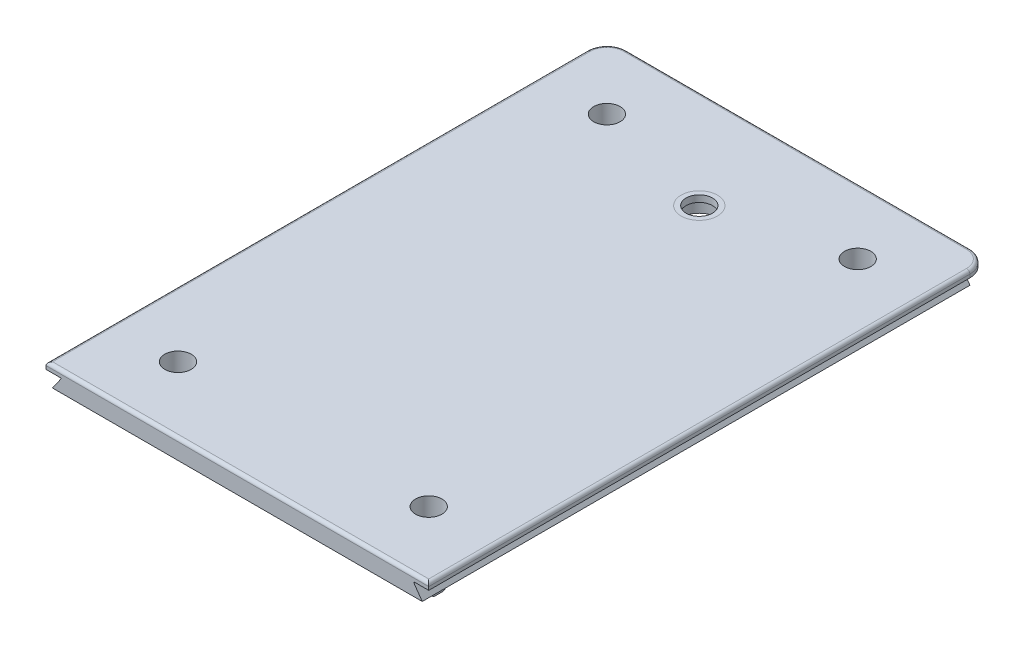
SolidWorks part; units mm, degrees
ref_plane "Front Plane" through (0, 0, 0) normal (0, 0, 1) x (1, 0, 0)
ref_plane "Top Plane" through (0, 0, 0) normal (0, 1, 0) x (1, 0, 0)
ref_plane "Right Plane" through (0, 0, 0) normal (1, 0, 0) x (0, 0, -1)
sketch "Sketch1" plane through (0, 0, 0) normal (0, 0, 1) x (1, 0, 0)
  line L0 (-29, 29) -> (-27, 29) construction
  line L1 (-29, 29) -> (-27, 29) construction
  line L2 (27, 29) -> (29, 29) construction
  line L3 (27, 29) -> (29, 29) construction
  line L4 (-27, 29) -> (-28.4004, 27)
  line L5 (-28.4004, 27) -> (28.4004, 27)
  line L6 (28.4004, 27) -> (27, 29)
  line L7 (27, 29) -> (-27, 29)
  line L8 (-27, 29) -> (-28.4004, 27) construction
  line L9 (-28.4004, 27) -> (28.4004, 27) construction
  line L10 (28.4004, 27) -> (27, 29) construction
  line L11 (27, 29) -> (-27, 29) construction
  line L12 (-26.7558, 29) -> (-28.0162, 27.2)
  line L13 (-28.0162, 27.2) -> (28.0162, 27.2)
  line L14 (28.0162, 27.2) -> (26.7558, 29)
  line L15 (-26.8362, 28.8853) -> (-28.0162, 27.2) construction
  line L16 (28.0162, 27.2) -> (26.8362, 28.8853) construction
  line L17 (26.7558, 29) -> (-26.7558, 29) construction
  line L18 (-26.7558, 29) -> (-26.7558, 29.15)
  line L19 (-26.7558, 29.15) -> (-29, 29.15)
  line L20 (-29, 29.15) -> (-29, 30.15)
  line L21 (0, 29) -> (0, 0.5) construction
  line L22 (0, 30.15) -> (0, 0.5) construction
  line L23 (-29, 30.15) -> (29, 30.15)
  line L24 (-29, 29) -> (-29, 0.5) construction
  line L25 (29, 29.15) -> (29, 30.15)
  line L26 (26.7558, 29.15) -> (29, 29.15)
  line L27 (26.7558, 29) -> (26.7558, 29.15)
  line L28 (27, 29) -> (-27, 29) construction
  dimension "D3" = 0.15
  dimension "D4" = 1
  dimension "D1" = 0
  dimension "D2" = 0.2
extrude "Boss-Extrude1" add sketch "Sketch1" against normal up to surface (83 mm away)
sketch "Sketch3" plane through (0, 0, -83) normal (0, 0, -1) x (-1, 0, 0)
  line L1 (-29, 30.15) -> (29, 30.15)
  line L2 (-29, 30.15) -> (-29, 29.15)
  line L3 (-29, 29.15) -> (29, 29.15)
  line L4 (29, 30.15) -> (29, 29.15)
extrude "Boss-Extrude2" add sketch "Sketch3" along normal up to surface (2 mm away)
fillet "Fillet1" radius 3 2 edges at (29, 29.65, -85) (-29, 29.65, -85)
sketch "Sketch4" plane through (0, 27.2, 0) normal (0, -1, 0) x (1, 0, 0)
  line L0 (28.0162, -83) -> (28.0162, 0) construction
  line L1 (28.0162, -1.5) -> (-28.0162, -1.5)
  line L2 (28.0162, -1.5) -> (28.0162, -3.5)
  line L3 (28.0162, -3.5) -> (-28.0162, -3.5)
  line L4 (-28.0162, -1.5) -> (-28.0162, -3.5)
  line L5 (-28.0162, -83) -> (-28.0162, 0) construction
  line L6 (-28.0162, 0) -> (28.0162, 0) construction
  dimension "D1" = 2
  dimension "D2" = 1.5
extrude "Boss-Extrude3" add sketch "Sketch4" along normal blind 0.25
fillet "Fillet2" radius 0.5 2 edges at (0, 26.95, -3.5) (0, 26.95, -1.5)
sketch "Sketch5" plane through (0, 30.15, 0) normal (0, 1, 0) x (1, 0, 0)
  line L0 (0, -16.3075) -> (0, 16.3075) construction
  line L1 (26, 85) -> (-26, 85) construction
  circle A0 centre (0, 70) radius 2.75
  dimension "D1" = 5.5
  dimension "D2" = 15
extrude "Cut-Extrude1" cut sketch "Sketch5" against normal up to next
sketch "Sketch6" plane through (0, 30.15, 0) normal (0, 1, 0) x (1, 0, 0)
  circle A0 centre (0, 70) radius 2.75 construction
  circle A1 centre (0, 70) radius 2.75
  circle A2 centre (0, 70) radius 2
  dimension "D1" = 0.75
extrude "Boss-Extrude4" add sketch "Sketch6" against normal blind 1 separate body
sketch "Sketch7" plane through (0, 30.15, 0) normal (0, 1, 0) x (1, 0, 0)
  line L0 (29, 0) -> (-29, 0) construction
  line L1 (29, 82) -> (29, 0) construction
  line L2 (29, 42.5) -> (-29, 42.5) construction
  line L4 (0, 0) -> (0, 85) construction
  line L5 (26, 85) -> (-26, 85) construction
  line L6 (-29, 82) -> (-29, 0) construction
  circle A0 centre (19, 10) radius 2
  circle A1 centre (19, 75) radius 2
  circle A2 centre (-19, 75) radius 2
  circle A3 centre (-19, 10) radius 2
  point P14 (0, 42.5)
  dimension "D1" = 4
  dimension "D2" = 10
  dimension "D3" = 10
extrude "Cut-Extrude2" cut sketch "Sketch7" against normal up to next (2.95 mm away)
fillet "Fillet3" radius 0.5 6 edges at (-29, 30.15, -41) (-28.1213, 30.15, -84.1213) (0, 30.15, -85) (28.1213, 30.15, -84.1213) (0, 30.15, 0) (29, 30.15, -41)
